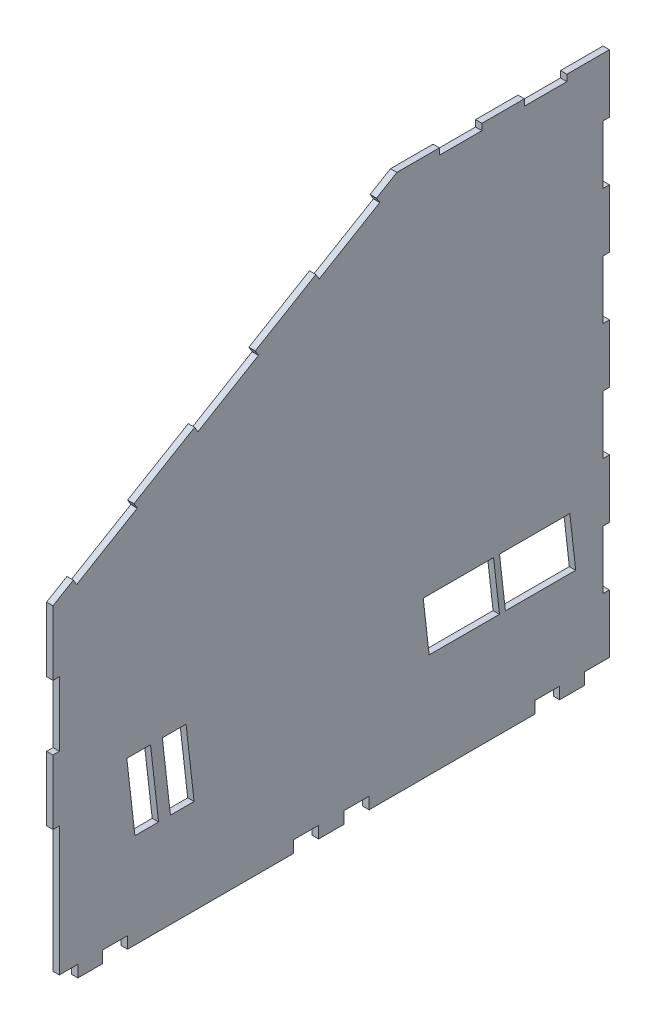
SolidWorks part; units mm, degrees
ref_plane "Ön Düzlem" through (0, 0, 0) normal (0, 0, 1) x (1, 0, 0)
ref_plane "Üst Düzlem" through (0, 0, 0) normal (0, 1, 0) x (1, 0, 0)
ref_plane "Sağ Düzlem" through (0, 0, 0) normal (1, 0, 0) x (0, 0, -1)
sketch "Sketch1" plane through (0, 0, 0) normal (1, 0, 0) x (0, 0, -1)
  line L0 (117.52, 112.5) -> (99.566, 112.5)
  line L6 (117.52, -109.8) -> (117.52, -85.1)
  line L13 (-107.0133, -112.5) -> (-107.0133, -114.8)
  line L14 (-6.4686, 92.2661) -> (-32.0795, 77.122)
  line L17 (27.75, 112.5) -> (19.1423, 107.4101)
  line L18 (-114.82, -109.8) -> (-107.0133, -109.8)
  line L20 (-107.0133, -114.8) -> (-96.5067, -114.8)
  line L21 (-86, -112.5) -> (-86, -114.8)
  line L22 (-114.82, -27.96) -> (-114.82, -0.68)
  line L23 (-117.52, -55.24) -> (-117.52, -27.96)
  line L24 (-96.5067, -114.8) -> (-96.5067, -112.5)
  line L25 (-117.52, -0.68) -> (-117.52, 26.6)
  line L26 (-117.52, -0.68) -> (-114.82, -0.68)
  line L27 (-117.52, -27.96) -> (-114.82, -27.96)
  line L28 (-114.82, -82.52) -> (-114.82, -55.24)
  line L29 (-117.52, -55.24) -> (-114.82, -55.24)
  line L31 (-86, -109.8) -> (-86, -112.5)
  line L32 (-107.0133, -109.8) -> (-107.0133, -112.5)
  line L33 (-96.5067, -109.8) -> (-96.5067, -112.5)
  line L34 (-96.5067, -109.8) -> (-86, -109.8)
  line L35 (-5.3333, -112.5) -> (-5.3333, -114.8)
  line L37 (-16, -112.5) -> (-16, -109.8)
  line L38 (-16, -109.8) -> (-5.3333, -109.8)
  line L39 (-5.3333, -114.8) -> (5.3333, -114.8)
  line L40 (-86, -114.8) -> (-16, -114.8)
  line L41 (5.3333, -109.8) -> (16, -109.8)
  line L42 (-5.3333, -109.8) -> (-5.3333, -112.5)
  line L43 (5.3333, -109.8) -> (5.3333, -112.5)
  line L44 (16, -109.8) -> (16, -112.5)
  line L45 (5.3333, -114.8) -> (5.3333, -112.5)
  line L46 (96.5067, -112.5) -> (96.5067, -114.8)
  line L47 (114.82, -35.7) -> (114.82, -11)
  line L48 (86, -109.8) -> (96.5067, -109.8)
  line L49 (96.5067, -114.8) -> (107.0133, -114.8)
  line L51 (86, -109.8) -> (86, -112.5)
  line L52 (96.5067, -109.8) -> (96.5067, -112.5)
  line L53 (107.0133, -109.8) -> (107.0133, -112.5)
  line L55 (107.0133, -109.8) -> (117.52, -109.8)
  line L56 (117.52, -60.4) -> (117.52, -35.7)
  line L57 (114.82, 13.7) -> (114.82, 38.4)
  line L58 (117.52, -11) -> (117.52, 13.7)
  line L59 (114.82, 63.1) -> (114.82, 87.8)
  line L60 (117.52, 38.4) -> (117.52, 63.1)
  line L61 (107.0133, -112.5) -> (107.0133, -114.8)
  line L62 (117.52, 87.8) -> (117.52, 112.5)
  line L63 (114.82, -85.1) -> (114.82, -60.4)
  line L64 (117.52, -85.1) -> (114.82, -85.1)
  line L65 (117.52, 13.7) -> (114.82, 13.7)
  line L66 (117.52, 87.8) -> (114.82, 87.8)
  line L67 (117.52, 63.1) -> (114.82, 63.1)
  line L68 (117.52, 38.4) -> (114.82, 38.4)
  line L69 (117.52, -11) -> (114.82, -11)
  line L70 (117.52, -35.7) -> (114.82, -35.7)
  line L71 (117.52, -60.4) -> (114.82, -60.4)
  line L72 (-57.6905, 61.978) -> (-83.3014, 46.8339)
  line L73 (-5.0944, 89.942) -> (-6.4686, 92.2661)
  line L74 (-107.538, 29.3658) -> (-81.9271, 44.5098)
  line L75 (-16, -114.8) -> (-16, -112.5)
  line L76 (99.566, 109.8) -> (81.612, 109.8)
  line L77 (16, -112.5) -> (16, -114.8)
  line L78 (63.658, 109.8) -> (45.704, 109.8)
  line L79 (-108.9123, 31.6899) -> (-117.52, 26.6)
  line L80 (45.704, 109.8) -> (45.704, 112.5)
  line L81 (63.658, 109.8) -> (63.658, 112.5)
  line L82 (81.612, 109.8) -> (81.612, 112.5)
  line L83 (99.566, 109.8) -> (99.566, 112.5)
  line L84 (16, -114.8) -> (86, -114.8)
  line L85 (86, -114.8) -> (86, -112.5)
  line L87 (-108.9123, 31.6899) -> (-107.538, 29.3658)
  line L88 (19.1423, 107.4101) -> (20.5165, 105.086)
  line L89 (-56.3162, 59.6539) -> (-30.7053, 74.7979)
  line L91 (-5.0944, 89.942) -> (20.5165, 105.086)
  line L92 (-30.7053, 74.7979) -> (-32.0795, 77.122)
  line L93 (-56.3162, 59.6539) -> (-57.6905, 61.978)
  line L94 (-81.9271, 44.5098) -> (-83.3014, 46.8339)
  line L95 (45.704, 112.5) -> (27.75, 112.5)
  line L97 (81.612, 112.5) -> (63.658, 112.5)
  line L98 (-114.82, -82.52) -> (-114.82, -109.8)
  line L209 (100.78, -48.8) -> (71.08, -48.8)
  line L211 (100.78, -70.8) -> (73.58, -70.8)
  line L212 (68.58, -48.8) -> (71.08, -70.8)
  line L215 (71.08, -48.8) -> (73.58, -70.8)
  line L216 (41.38, -48.8) -> (38.88, -48.8)
  line L217 (38.88, -48.8) -> (41.38, -70.8)
  line L218 (100.78, -70.8) -> (103.28, -70.8)
  line L219 (100.78, -48.8) -> (103.28, -70.8)
  line L220 (71.08, -70.8) -> (41.38, -70.8)
  line L221 (68.58, -48.8) -> (41.38, -48.8)
  line L226 (-72.9109, -74.8) -> (-76.32, -44.8)
  line L227 (-67.9109, -74.8) -> (-71.32, -44.8)
  line L233 (-82.9109, -74.8) -> (-86.32, -44.8)
  line L235 (-57.9109, -74.8) -> (-61.32, -44.8)
  line L238 (-62.9109, -74.8) -> (-66.32, -44.8) [skipped]
  line L239 (-76.32, -44.8) -> (-86.32, -44.8)
  line L240 (-82.9109, -74.8) -> (-72.9109, -74.8)
  line L241 (-67.9109, -74.8) -> (-57.9109, -74.8)
  line L242 (-71.32, -44.8) -> (-61.32, -44.8)
  point P0 (0, 0)
  dimension "D1" = 3
extrude "Boss-Extrude1" add sketch "Sketch1" along normal blind 2.7 contours L82 L97 L81 L78 L80 L95 L17 L88 L91 L73 L14 L92 L89 L93 L72 L94 L74 L87 L79 L25 L26 L22 L27 L23 L29 L28 L18 L32 L33 L34 L31 L37 L38 L42 L43 L41 L44 L51 L48 L52 L53 region at (0, -10.1848, -8.605)
ref_plane "Plane1" through (2.7, 112.5, -27.75) normal (0, -0.509, 0.8608) x (1, 0, 0)
